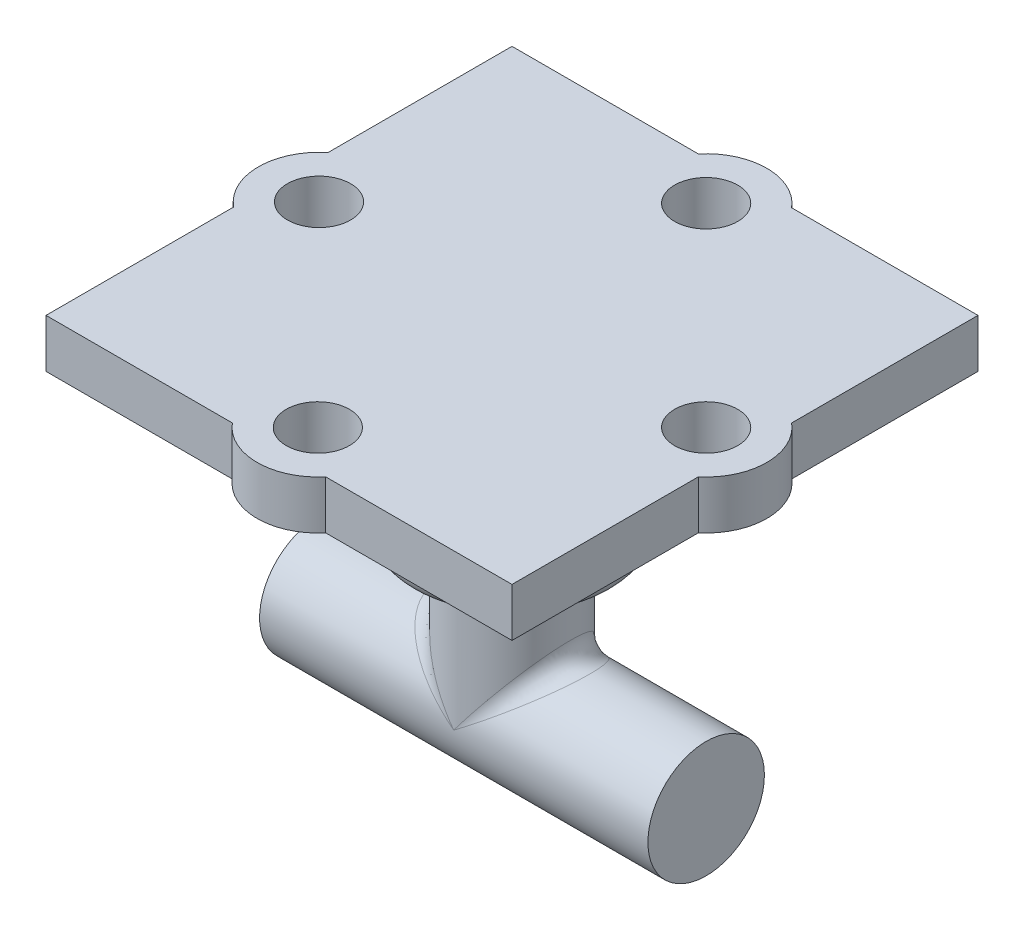
SolidWorks part; units mm, degrees
ref_plane "Спереди" through (0, 0, 0) normal (0, 0, 1) x (1, 0, 0)
ref_plane "Сверху" through (0, 0, 0) normal (0, 1, 0) x (1, 0, 0)
ref_plane "Справа" through (0, 0, 0) normal (1, 0, 0) x (0, 0, -1)
sketch "Sketch1" plane through (0, 0, 0) normal (0, 1, 0) x (1, 0, 0)
  line L0 (-24, -4.6689) -> (-24, -24)
  line L1 (-24, 24) -> (-4.8023, 24)
  line L2 (-24, 24) -> (-24, 5.0436)
  line L3 (-24, -24) -> (-4.8023, -24)
  line L4 (24, 24) -> (24, 4.8023)
  line L5 (-24, 24) -> (24, -24) construction
  line L6 (-24, -24) -> (24, 24) construction
  line L7 (-16, 16) -> (-4.8023, 16)
  line L8 (-16, 16) -> (-16, 4.9342)
  line L9 (-16, -16) -> (-4.8023, -16)
  line L10 (16, 16) -> (16, 4.8023)
  line L11 (-16, 16) -> (16, -16) construction
  line L12 (-16, -16) -> (16, 16) construction
  line L13 (-16, -4.5595) -> (-16, -16)
  line L14 (4.8023, 16) -> (16, 16)
  line L15 (4.8023, 24) -> (24, 24)
  line L16 (16, -4.8023) -> (16, -16)
  line L17 (4.8023, -16) -> (16, -16)
  line L18 (4.8023, -24) -> (24, -24)
  line L19 (24, -4.8023) -> (24, -24)
  circle A0 centre (-20.0657, 0.1873) radius 3.25
  circle A1 centre (0, 20) radius 3.25
  circle A2 centre (20, 0) radius 3.25
  circle A3 centre (0, -20) radius 3.25
  arc A4 (12, -16) -> (6.1732, -19.0234) centre (0, 0) ccw construction
  arc A5 (-24, 5.0436) -> (-24, -4.6689) centre (-20.0657, 0.1873) ccw
  arc A6 (-4.8023, 16) -> (4.8023, 16) centre (0, 20) ccw
  arc A7 (16, 4.8023) -> (16, -4.8023) centre (20, 0) ccw
  arc A8 (4.8023, -16) -> (-4.8023, -16) centre (0, -20) ccw
  arc A9 (-16, -4.5595) -> (-16, 4.9342) centre (-20.0657, 0.1873) ccw
  arc A10 (4.8023, 24) -> (-4.8023, 24) centre (0, 20) ccw
  arc A11 (24, -4.8023) -> (24, 4.8023) centre (20, 0) ccw
  arc A12 (-4.8023, -24) -> (4.8023, -24) centre (0, -20) ccw
  point P0 (0, 0)
  point P6 (0, 0)
  dimension "D3" = 40
  dimension "D4" = 6.5
  dimension "D5" = 12.5
  dimension "D6" = 6.5
  dimension "D7" = 12.5
  dimension "D8" = 6.5
  dimension "D9" = 12.5
  dimension "D10" = 6.5
  dimension "D11" = 12.5
  dimension "D1" = 48
  dimension "D2" = 32
  dimension "D12" = 32
extrude "Boss-Extrude1" add sketch "Sketch1" along normal blind 5 contours L4 A11 L19 L18 A12 L3 L0 A5 L2 L1 A10 L15 | A8 L9 L13 A9 L8 L7 A6 L14 L10 A7 L16 L17 | A1 | A3 | A2 | A0
ref_plane "Plane1" through (0, -65, 0) normal (0, -1, 0) x (-1, 0, 0)
sketch "Sketch2" plane through (0, 0, 0) normal (0, -1, 0) x (1, 0, 0)
  line L1 (-16.3247, -16.4535) -> (16.3247, -16.4535)
  line L2 (-16.3247, -16.4535) -> (-16.3247, 16.4535)
  line L3 (-16.3247, 16.4535) -> (16.3247, 16.4535)
  line L4 (16.3247, -16.4535) -> (16.3247, 16.4535)
  line L5 (-16.3247, -16.4535) -> (16.3247, 16.4535) construction
  line L6 (-16.3247, 16.4535) -> (16.3247, -16.4535) construction
  point P0 (0, 0)
extrude "Boss-Extrude2" add sketch "Sketch2" against normal up to surface (5 mm away) up to face at (20, 5, 3.25)
sketch "Sketch3" plane through (0, 0, 0) normal (0, -1, 0) x (-1, 0, 0)
  circle A0 centre (0, 0) radius 10.5672
extrude "Boss-Extrude3" add sketch "Sketch3" along normal blind 15
sketch "Sketch4" plane through (0, -15, 0) normal (0, -1, 0) x (-1, 0, 0)
  circle A0 centre (0, 0) radius 6
extrude "Boss-Extrude4" add sketch "Sketch4" along normal blind 14
sketch "Sketch5" plane through (0, 0, 0) normal (1, 0, 0) x (0, 0, -1)
  line L1 (-6, -29) -> (6, -29) construction
  circle A0 centre (0, -29) radius 6
  point P2 (-0.6059, -38.4421)
  point P3 (0, -40.0825)
  point P4 (0, 0)
  point P6 (0, -39.6379)
  point P7 (0, -39.5507)
  point P8 (0, -40.5109)
  point P9 (0, 0)
  point P10 (0, 0)
  point P12 (0, -35)
extrude "Boss-Extrude5" add sketch "Sketch5" along normal mid plane 40
fillet "Fillet3" radius 2 2 edges at (-6, -23, 0) (6, -23, 0)
fillet "Fillet1" radius 2 3 edges at (0, -15, -6) (0, 0, 10.5672) (0, -15, -10.5672)
